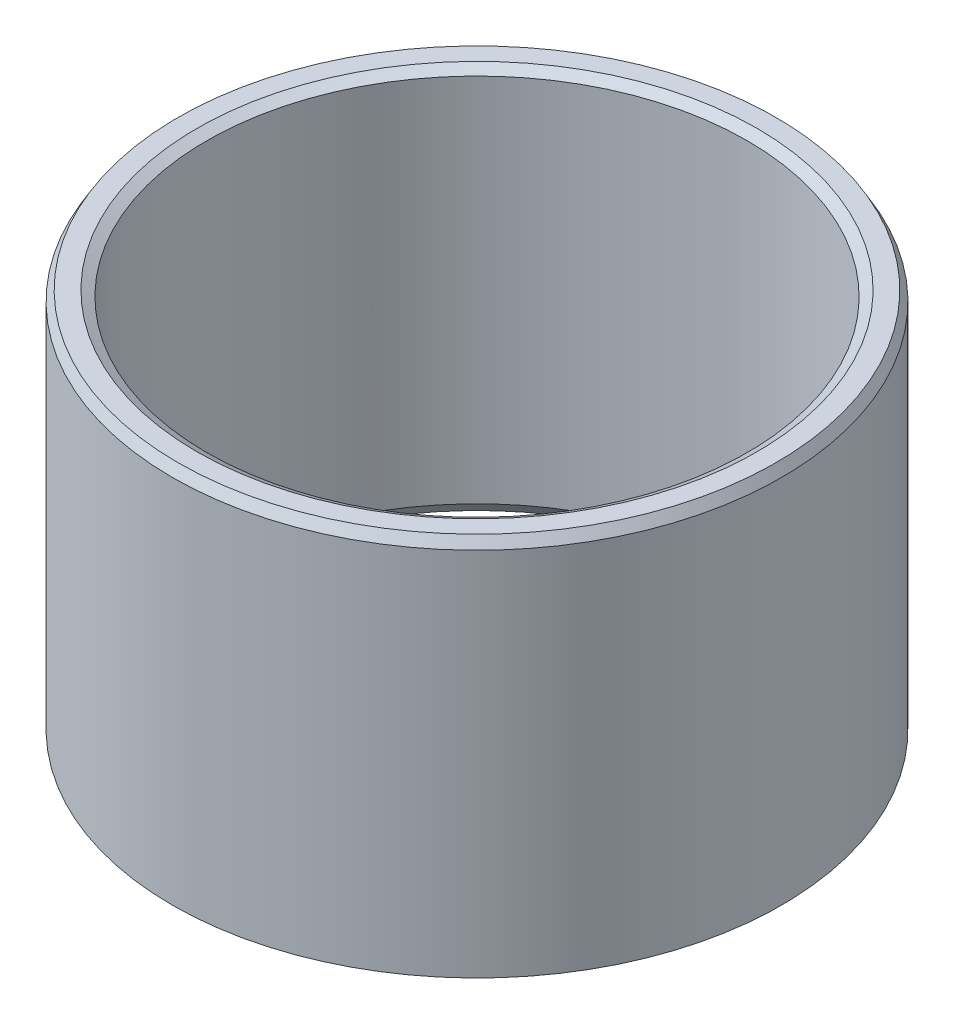
SolidWorks part; units mm, degrees
ref_plane "Front Plane" through (0, 0, 0) normal (0, 0, 1) x (1, 0, 0)
ref_plane "Top Plane" through (0, 0, 0) normal (0, 1, 0) x (1, 0, 0)
ref_plane "Right Plane" through (0, 0, 0) normal (1, 0, 0) x (0, 0, -1)
sketch "Sketch1" plane through (0, 0, 0) normal (0, 1, 0) x (1, 0, 0)
  circle A0 centre (0, 0) radius 52.5
  dimension "SLEEVE_OD" = 105
extrude "Boss-Extrude1" add sketch "Sketch1" along normal blind 66.5106
sketch "Sketch2" plane through (0, 0, 0) normal (0, 1, 0) x (1, 0, 0)
  circle A0 centre (0, 0) radius 46.5535
  dimension "BORE_D" = 93.1069
extrude "Cut-Extrude1" cut sketch "Sketch2" along normal through all
chamfer "Chamfer1" distance 1.7038 angle 30 4 edges at (0, 66.5106, 46.5535) (0, 0, 46.5535) (0, 0, 52.5) (0, 66.5106, 52.5) first distance on face at (0, 66.5106, 46.5535) first distance on face at (0, 0, 46.5535) first distance on face at (0, 66.5106, 52.5)
